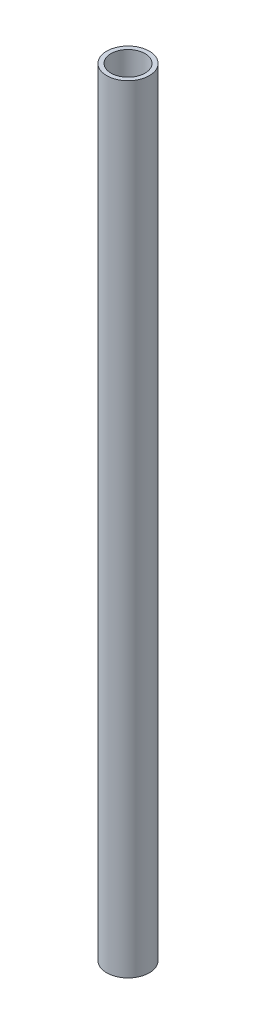
SolidWorks part; units mm, degrees
material "Plain Carbon Steel"
ref_plane "Front Plane" through (0, 0, 0) normal (0, 0, 1) x (1, 0, 0)
ref_plane "Top Plane" through (0, 0, 0) normal (0, 1, 0) x (1, 0, 0)
ref_plane "Right Plane" through (0, 0, 0) normal (1, 0, 0) x (0, 0, -1)
sketch "Sketch1" plane through (0, 0, 0) normal (0, 1, 0) x (1, 0, 0)
  circle A0 centre (0, 0) radius 16.7005
  circle A1 centre (0, 0) radius 13.3223
  dimension "D1" = 33.401
  dimension "D2" = 26.6446
extrude "Boss-Extrude1" add sketch "Sketch1" along normal blind 609.6
